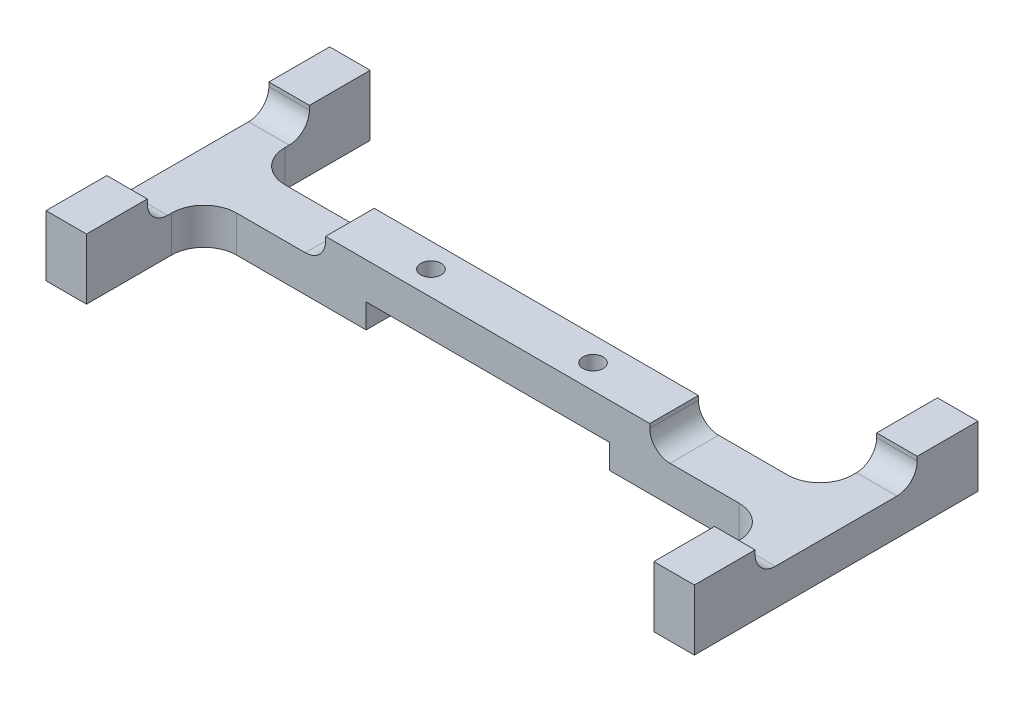
SolidWorks part; units mm, degrees
ref_plane "Front Plane" through (0, 0, 0) normal (0, 0, 1) x (1, 0, 0)
ref_plane "Top Plane" through (0, 0, 0) normal (0, 1, 0) x (1, 0, 0)
ref_plane "Right Plane" through (0, 0, 0) normal (1, 0, 0) x (0, 0, -1)
sketch "Sketch1" plane through (0, 0, 0) normal (0, 1, 0) x (1, 0, 0)
  line L1 (-50.8, -22.225) -> (50.8, -22.225)
  line L2 (-50.8, -22.225) -> (-50.8, 22.225)
  line L3 (-50.8, 22.225) -> (50.8, 22.225)
  line L4 (50.8, -22.225) -> (50.8, 22.225)
  line L5 (-50.8, -22.225) -> (50.8, 22.225) construction
  line L6 (-50.8, 22.225) -> (50.8, -22.225) construction
  point P0 (0, 0)
  dimension "D1" = 101.6
  dimension "D2" = 44.45
extrude "Boss-Extrude1" add sketch "Sketch1" along normal blind 9.525
sketch "Sketch2" plane through (0, 9.525, 0) normal (0, 1, 0) x (1, 0, 0)
  line L0 (-50.8, -22.225) -> (50.8, -22.225) construction
  line L1 (-44.45, -22.225) -> (44.45, -22.225)
  line L2 (-44.45, -22.225) -> (-44.45, -3.81)
  line L3 (-44.45, -3.81) -> (44.45, -3.81)
  line L4 (44.45, -22.225) -> (44.45, -3.81)
  line L5 (-50.8, 22.225) -> (-50.8, -22.225) construction
  line L6 (50.8, -22.225) -> (50.8, 22.225) construction
  dimension "D1" = 6.35
  dimension "D2" = 6.35
  dimension "D3" = 3.81
extrude "Cut-Extrude1" cut sketch "Sketch2" against normal through all
mirror "Mirror1" about plane through (0, 0, 0) normal (0, 0, 1) of "Cut-Extrude1"
fillet "Fillet1" radius 5.08 4 edges at (44.45, 4.7625, -3.81) (44.45, 4.7625, 3.81) (-44.45, 4.7625, 3.81) (-44.45, 4.7625, -3.81)
sketch "Sketch3" plane through (0, 9.525, 0) normal (0, 1, 0) x (1, 0, 0)
  line L0 (-50.8, 22.225) -> (-50.8, -22.225) construction
  line L1 (-50.8, 12.7) -> (-25.4, 12.7)
  line L2 (-50.8, 12.7) -> (-50.8, -12.7)
  line L3 (-50.8, -12.7) -> (-25.4, -12.7)
  line L4 (-25.4, 12.7) -> (-25.4, -12.7)
  dimension "D1" = 12.7
  dimension "D2" = 12.7
  dimension "D3" = 25.4
extrude "Cut-Extrude2" cut sketch "Sketch3" against normal blind 3.81
mirror "Mirror2" about plane through (0, 0, 0) normal (1, 0, 0) of "Cut-Extrude2"
fillet "Fillet2" radius 3.175 6 edges at (-25.4, 5.715, 0) (25.4, 5.715, 0) (47.625, 5.715, 12.7) (47.625, 5.715, -12.7) (-47.625, 5.715, 12.7) (-47.625, 5.715, -12.7)
sketch "Sketch4" plane through (0, 0, 0) normal (0, -1, 0) x (1, 0, 0)
  circle A0 centre (-12.7, 0) radius 1.5875
  point P2 (0, 0)
  dimension "D1" = 3.175
  dimension "D2" = 12.7
extrude "Cut-Extrude3" cut sketch "Sketch4" against normal through all
sketch "Sketch5" plane through (0, 0, 0) normal (0, -1, 0) x (1, 0, 0)
  line L0 (39.37, 3.81) -> (-39.37, 3.81) construction
  line L1 (-19.05, 3.81) -> (19.05, 3.81)
  line L2 (-19.05, 3.81) -> (-19.05, -3.81)
  line L3 (-19.05, -3.81) -> (19.05, -3.81)
  line L4 (19.05, 3.81) -> (19.05, -3.81)
  line L5 (39.37, -3.81) -> (-39.37, -3.81) construction
  dimension "D1" = 19.05
  dimension "D2" = 19.05
extrude "Cut-Extrude4" cut sketch "Sketch5" against normal blind 3.81
mirror "Mirror3" about plane through (0, 0, 0) normal (1, 0, 0) of "Cut-Extrude3"
